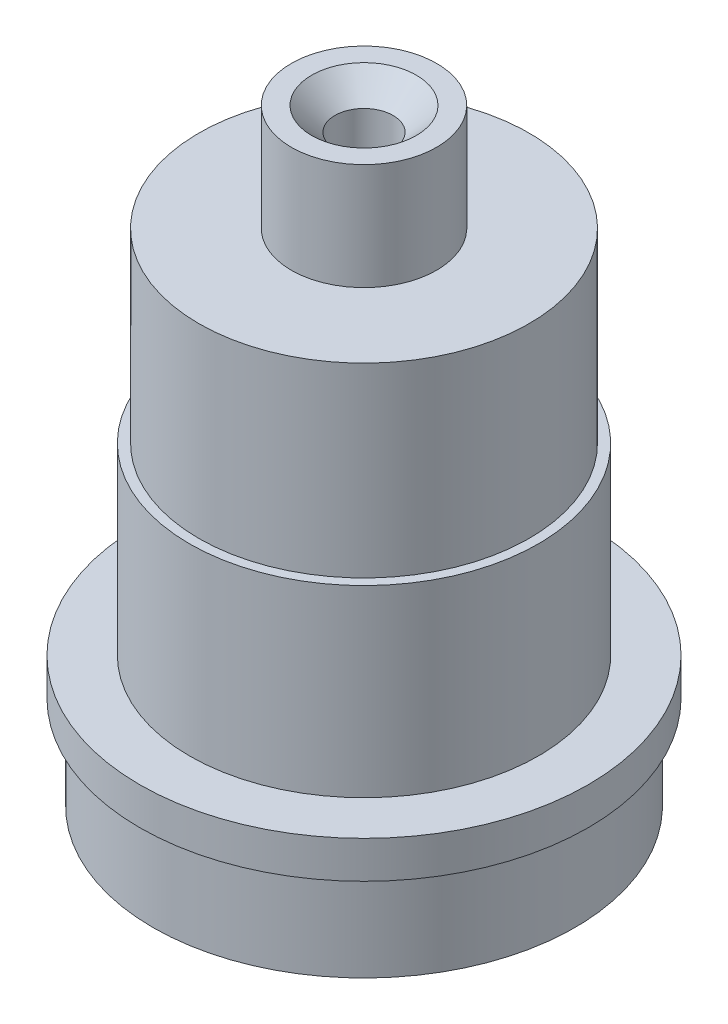
SolidWorks part; units mm, degrees
material "6061-T6 (SS)"
ref_plane "Front Plane" through (0, 0, 0) normal (0, 0, 1) x (1, 0, 0)
ref_plane "Top Plane" through (0, 0, 0) normal (0, 1, 0) x (1, 0, 0)
ref_plane "Right Plane" through (0, 0, 0) normal (1, 0, 0) x (0, 0, -1)
sketch "Sketch1" plane through (0, 0, 0) normal (0, 1, 0) x (1, 0, 0)
  circle A0 centre (0, 0) radius 23.0505
  dimension "D1" = 46.101
extrude "Boss-Extrude1" add sketch "Sketch1" along normal blind 10.16
sketch "Sketch2" plane through (0, 10.16, 0) normal (0, 1, 0) x (1, 0, 0)
  circle A0 centre (0, 0) radius 24.4856
  dimension "D1" = 48.9712
extrude "Boss-Extrude2" add sketch "Sketch2" along normal blind 4.064
sketch "Sketch3" plane through (0, 14.224, 0) normal (0, 1, 0) x (1, 0, 0)
  circle A0 centre (0, 0) radius 19.05
  dimension "D1" = 38.1
extrude "Boss-Extrude3" add sketch "Sketch3" along normal blind 20.066
sketch "Sketch4" plane through (0, 34.29, 0) normal (0, 1, 0) x (1, 0, 0)
  circle A0 centre (0, 0) radius 18.034
  dimension "D1" = 36.068
extrude "Boss-Extrude4" add sketch "Sketch4" along normal blind 20.32
sketch "Sketch5" plane through (0, 54.61, 0) normal (0, 1, 0) x (1, 0, 0)
  circle A0 centre (0, 0) radius 7.9375
  dimension "D1" = 15.875
extrude "Boss-Extrude5" add sketch "Sketch5" along normal blind 11.6332
sketch "Sketch6" plane through (0, 0, 0) normal (0, 0, 1) x (1, 0, 0)
  line L0 (6.35, 66.2432) -> (6.35, 67.7672)
  line L1 (7.9375, 66.2432) -> (-7.9375, 66.2432) construction
  line L2 (6.35, 67.7672) -> (3.3655, 67.7672)
  line L3 (3.3655, 67.7672) -> (3.3655, 71.8312)
  line L4 (3.3655, 71.8312) -> (7.112, 71.8312)
  line L5 (7.112, 71.8312) -> (7.112, 76.1492)
  line L6 (7.112, 76.1492) -> (0, 76.1492)
  line L7 (0, 76.1492) -> (0, 66.2432)
  line L8 (0, 66.2432) -> (6.35, 66.2432)
  dimension "D1" = 6.35
  dimension "D2" = 1.524
  dimension "D3" = 4.064
  dimension "D4" = 4.318
  dimension "D5" = 7.112
  dimension "D6" = 3.3655
revolve "Revolve1" [suppressed] add sketch "Sketch6" angle 360 about L7
fillet "Fillet1" [suppressed] radius 1.27
sketch "Sketch7" plane through (0, 66.2432, 0) normal (0, 1, 0) x (1, 0, 0)
  circle A0 centre (0, 0) radius 3.175
  dimension "D1" = 6.35
extrude "Cut-Extrude1" cut sketch "Sketch7" against normal blind 17.018
chamfer "Chamfer1" distance 2.54 angle 45 1 edges at (0, 66.2432, 3.175)
